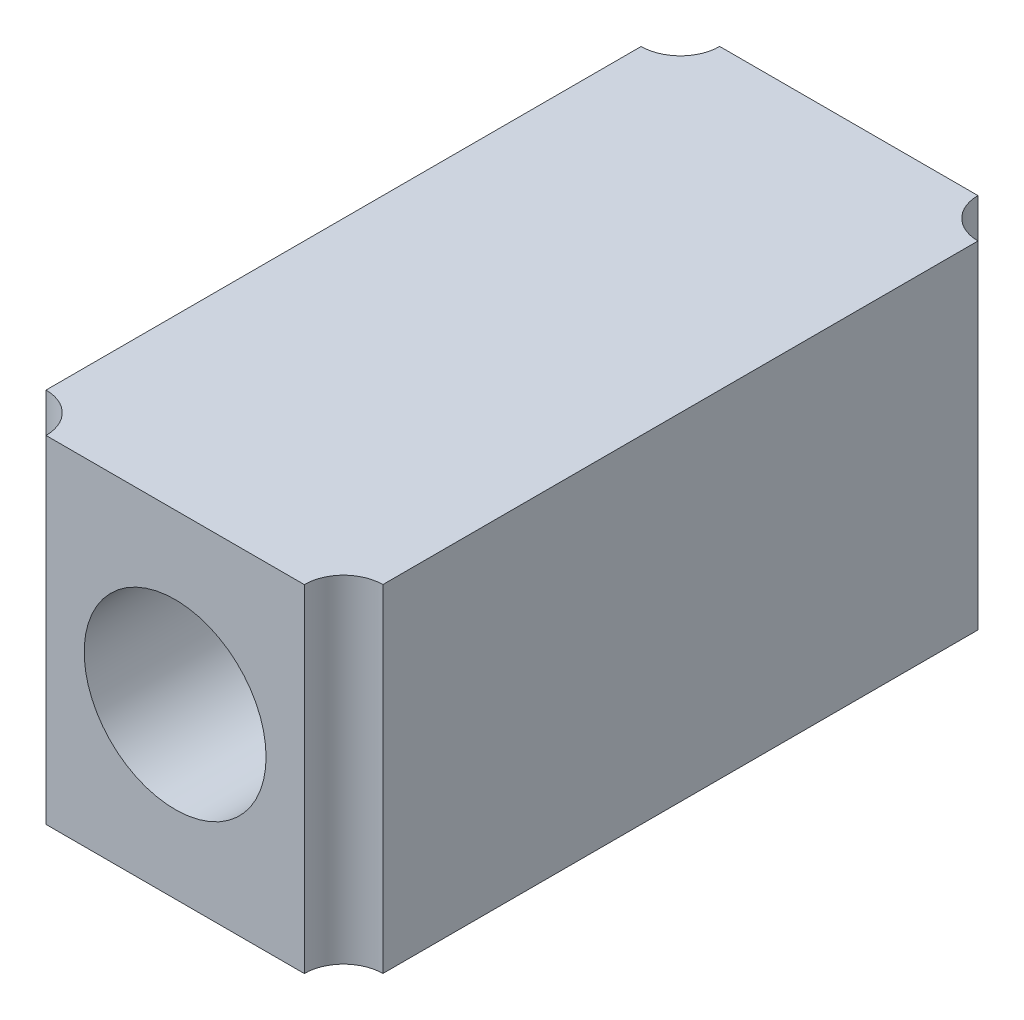
SolidWorks part; units mm, degrees
material "Polyetheretherketone (PEEK)"
ref_plane "Front Plane" through (0, 0, 0) normal (0, 0, 1) x (1, 0, 0)
ref_plane "Top Plane" through (0, 0, 0) normal (0, 1, 0) x (1, 0, 0)
ref_plane "Right Plane" through (0, 0, 0) normal (1, 0, 0) x (0, 0, -1)
sketch "Sketch1" plane through (0, 0, 0) normal (0, 0, 1) x (1, 0, 0)
  line L1 (-7.5, -7.5) -> (7.5, -7.5)
  line L2 (-7.5, -7.5) -> (-7.5, 7.5)
  line L3 (-7.5, 7.5) -> (7.5, 7.5)
  line L4 (7.5, -7.5) -> (7.5, 7.5)
  line L5 (-7.5, -7.5) -> (7.5, 7.5) construction
  line L6 (-7.5, 7.5) -> (7.5, -7.5) construction
  circle A0 centre (0, 0) radius 4.05
  dimension "D3" = 8.1
  dimension "D1" = 15
  dimension "D2" = 15
extrude "Boss-Extrude1" add sketch "Sketch1" along normal blind 30
ref_axis "Axis1" through (0, 0, -1.5) along (0, 0, 1)
sketch "Sketch2" plane through (0, 7.5, 0) normal (0, 1, 0) x (1, 0, 0)
  circle A0 centre (7.5, -30) radius 1.75
  circle A1 centre (7.5, 0) radius 1.75
  circle A2 centre (-7.5, 0) radius 1.75
  circle A3 centre (-7.5, -30) radius 1.75
  dimension "D1" = 3.5
extrude "Cut-Extrude1" cut sketch "Sketch2" against normal through all
